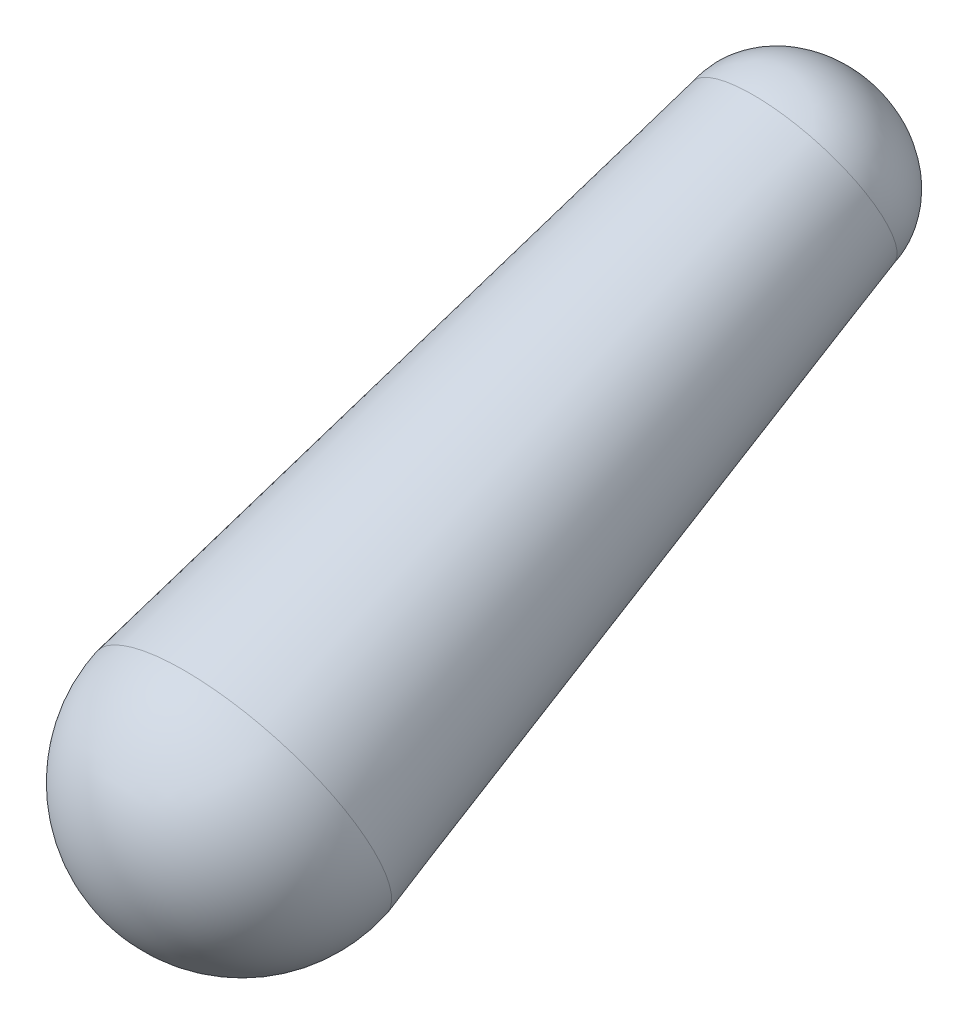
SolidWorks part; units mm, degrees
ref_plane "Front Plane" through (0, 0, 0) normal (0, 0, 1) x (1, 0, 0)
ref_plane "Top Plane" through (0, 0, 0) normal (0, 1, 0) x (1, 0, 0)
ref_plane "Right Plane" through (0, 0, 0) normal (1, 0, 0) x (0, 0, -1)
sketch "Top Contour" plane through (0, 0, 0) normal (1, 0, 0) x (0, 0, -1)
  line L0 (189.3211, -51.6959) -> (211.711, -60.626) construction
  line L1 (189.3211, -51.6959) -> (149.4591, -69.9444) construction
  line L2 (149.4591, -69.9444) -> (126.4413, -51.6959) construction
ref_plane "Plane1" through (0, -69.9444, -149.4591) normal (0, -0.4162, 0.9093) x (1, 0, 0)
sketch "Sketch1" plane through (0, -69.9444, -149.4591) normal (0, -0.4162, 0.9093) x (1, 0, 0)
  circle A0 centre (0, 0) radius 10
extrude "Boss-Extrude1" add sketch "Sketch1" against normal up to vertex (43.8404 mm away) draft 4 up to point (0, -51.6959, -189.3211)
dome "Dome1" faces to dome 1 distance 10 reverse direction no elliptical dome no face at (0, -79.0369, -153.6216) parameters "D1"=10
dome "Dome2" faces to dome 1 distance 6 reverse direction no elliptical dome yes face at (0, -58.001, -192.2075) parameters "D1"=6
ref_axis "Axis1" through (0, -69.9444, -149.4591) along (1, 0, 0)
ref_axis "Axis2" through (0, -51.6959, -189.3211) along (1, 0, 0)
